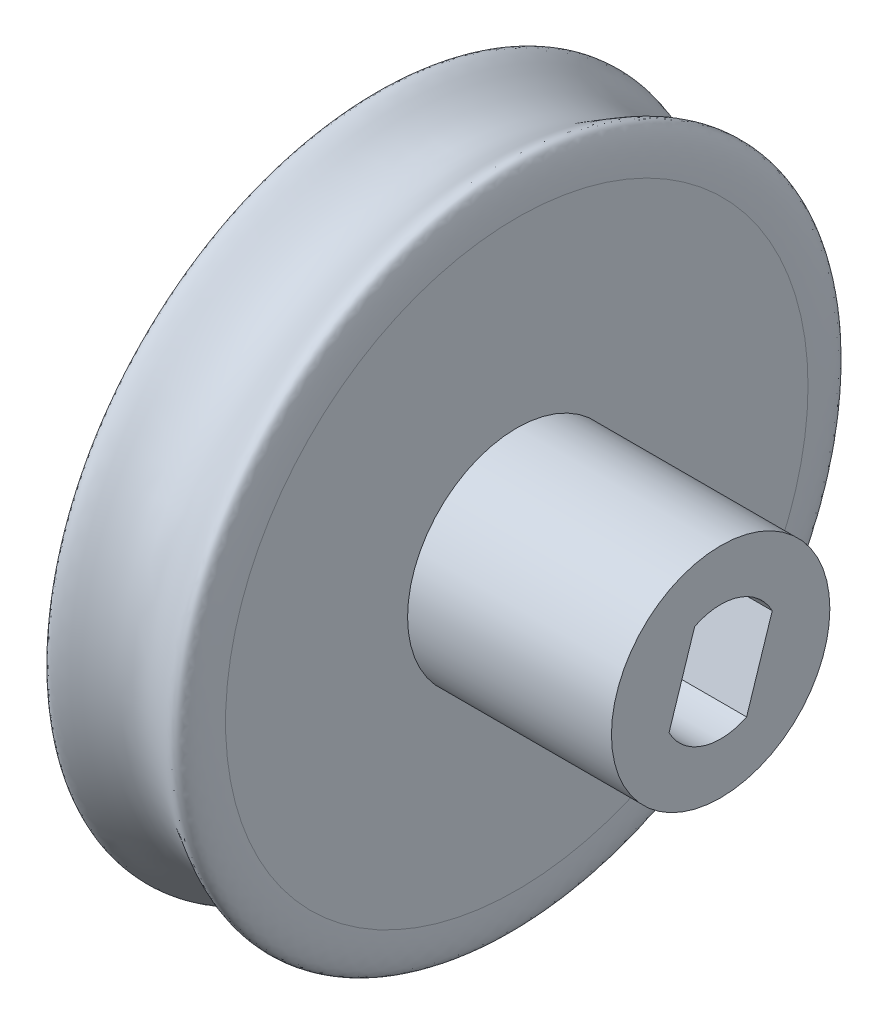
SolidWorks part; units mm, degrees
ref_plane "Front Plane" through (0, 0, 0) normal (0, 0, 1) x (1, 0, 0)
ref_plane "Top Plane" through (0, 0, 0) normal (0, 1, 0) x (1, 0, 0)
ref_plane "Right Plane" through (0, 0, 0) normal (1, 0, 0) x (0, 0, -1)
sketch "Sketch1" plane through (0, 0, 0) normal (0, 0, 1) x (1, 0, 0)
  line L0 (0, 0) -> (-3.175, 0)
  line L1 (-3.175, 0) -> (-3.175, 12.7)
  line L2 (0, 0) -> (3.175, 0)
  line L3 (3.175, 0) -> (3.175, 12.7)
  line L4 (-3.175, 12.7) -> (-3.175, 19.05) construction
  line L5 (-3.175, 19.05) -> (0, 6.35) construction
  line L6 (0, 6.35) -> (3.175, 19.05) construction
  line L7 (3.175, 19.05) -> (3.175, 12.7) construction
  spline S0 degree 4 poles (-3.175, 12.7) (-3.175, 19.05) (0, 6.35) (3.175, 19.05) (3.175, 12.7) knots 0 0 0 0 0 1 1 1 1 1
  point P9 (0, 0)
  point P10 (0, 0)
  point P11 (0, 20.8471)
  point P12 (3.175, 29.9337)
  dimension "D1" = 6.35
  dimension "D2" = 12.7
  dimension "D3" = 6.35
  dimension "D4" = 6.35
revolve "Revolve1" add sketch "Sketch1" angle 360 about L0
sketch "Sketch2" plane through (3.175, 0, 0) normal (1, 0, 0) x (0, 0, -1)
  line L0 (1.1327, -2.2734) -> (2.2503, 1.178)
  line L1 (-1.1327, 2.2734) -> (-2.2503, -1.178)
  circle A0 centre (0, 0) radius 4.7625
  arc A1 (-2.2503, -1.178) -> (1.1327, -2.2734) centre (0, 0) ccw
  arc A2 (2.2503, 1.178) -> (-1.1327, 2.2734) centre (0, 0) ccw
extrude "Boss-Extrude1" add sketch "Sketch2" along normal blind 8.89
extrude "Cut-Extrude1" cut sketch "Sketch2<2>" against normal blind 3.175 contours L1 A1 L0 A2
sketch "Sketch2<2>" plane through (3.175, 0, 0) normal (1, 0, 0) x (0, 0, -1) same geometry as "Sketch2"
